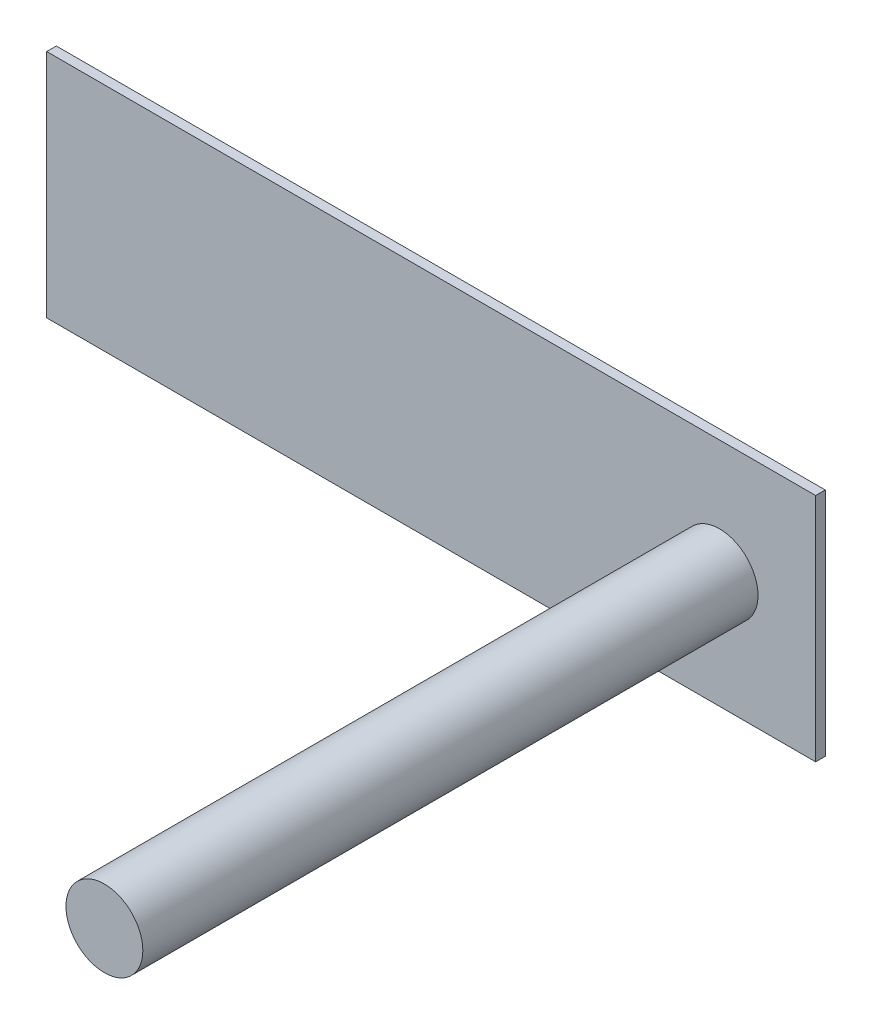
SolidWorks part; units mm, degrees
ref_plane "Front Plane" through (0, 0, 0) normal (0, 0, 1) x (1, 0, 0)
ref_plane "Top Plane" through (0, 0, 0) normal (0, 1, 0) x (1, 0, 0)
ref_plane "Right Plane" through (0, 0, 0) normal (1, 0, 0) x (0, 0, -1)
sketch "Sketch2" plane through (0, 0, 0) normal (0, 0, 1) x (1, 0, 0)
  line L4 (63.5, 38.1) -> (-63.5, 38.1)
  line L5 (63.5, -38.1) -> (63.5, 38.1)
  line L6 (-63.5, -38.1) -> (63.5, -38.1)
  line L7 (-63.5, 38.1) -> (-63.5, -38.1)
  line L8 (63.5, 38.1) -> (-63.5, 38.1)
  line L9 (63.5, -38.1) -> (63.5, 38.1)
  line L10 (-63.5, -38.1) -> (63.5, -38.1)
  line L11 (-63.5, 38.1) -> (-63.5, -38.1)
  circle A1 centre (25.4, 0) radius 12.7
  circle A2 centre (25.4, 0) radius 12.7
  dimension "D1" = 0
  dimension "D2" = 0
sketch "Sketch3" plane through (0, 0, 0) normal (0, 1, 0) x (1, 0, 0)
  line L4 (-63.5, 12.7) -> (-63.5, -25.4)
  line L5 (-63.5, -25.4) -> (63.5, -25.4)
  line L6 (63.5, -25.4) -> (63.5, 0)
  line L7 (-18.5941, 12.7) -> (-63.5, 12.7)
  line L8 (-63.5, 12.7) -> (-63.5, -25.4)
  line L9 (-63.5, -25.4) -> (63.5, -25.4)
  line L10 (63.5, -25.4) -> (63.5, 0)
  line L11 (-18.5941, 12.7) -> (-63.5, 12.7)
  arc A3 (63.5, 0) -> (25.4, 38.1) centre (25.4, 0) ccw
  arc A4 (25.4, 38.1) -> (-7.5956, 19.05) centre (25.4, 0) ccw
  arc A5 (-18.5941, 12.7) -> (-7.5956, 19.05) centre (-18.5941, 25.4) ccw
  arc A6 (63.5, 0) -> (25.4, 38.1) centre (25.4, 0) ccw
  arc A7 (25.4, 38.1) -> (-7.5956, 19.05) centre (25.4, 0) ccw
  arc A8 (-18.5941, 12.7) -> (-7.5956, 19.05) centre (-18.5941, 25.4) ccw
  dimension "D1" = 0
sketch "Sketch6" plane through (0, 0, 0) normal (0, 1, 0) x (1, 0, 0)
  line L0 (25.4, 88.9) -> (25.4, -76.2) construction
  line L1 (25.4, 88.9) -> (25.4, -76.2)
sketch "Sketch4" plane through (0, 0, 0) normal (0, 0, 1) x (1, 0, 0)
  circle A0 centre (25.4, 0) radius 12.7 construction
  circle A1 centre (25.4, 0) radius 12.7 construction
  circle A2 centre (25.4, 0) radius 10.16
  dimension "D1" = 2.54
extrude "Boss-Extrude1" add sketch "Sketch4" along normal up to vertex (76.2 mm away) and the other way up to vertex (88.9 mm away) up to point (25.4, 0, 76.2) other way up to point (25.4, 0, -88.9)
sketch "Sketch7" plane through (0, 0, -88.9) normal (0, 0, -1) x (-1, 0, 0)
  line L0 (152.4, 30.48) -> (152.4, -30.48) construction
  line L1 (-50.8, -30.48) -> (152.4, -30.48)
  line L2 (-50.8, -30.48) -> (-50.8, 30.48)
  line L3 (-50.8, 30.48) -> (152.4, 30.48)
  line L4 (152.4, -30.48) -> (152.4, 30.48)
  line L5 (152.4, -30.48) -> (63.5, -30.48) construction
  dimension "D1" = 25.4
extrude "Boss-Extrude2" add sketch "Sketch7" against normal blind 2.54
